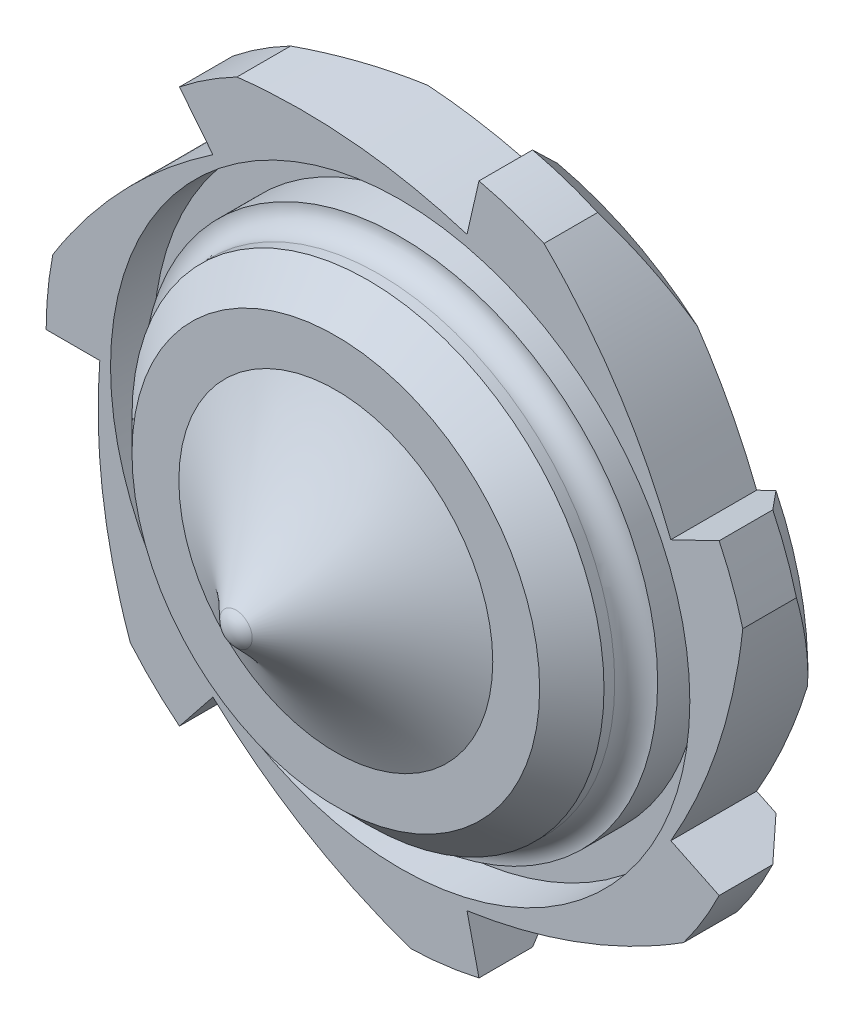
SolidWorks part; units mm, degrees
ref_plane "Plan de face" through (0, 0, 0) normal (0, 0, 1) x (1, 0, 0)
ref_plane "Plan de dessus" through (0, 0, 0) normal (0, 1, 0) x (1, 0, 0)
ref_plane "Plan de droite" through (0, 0, 0) normal (1, 0, 0) x (0, 0, -1)
sketch "Esquisse1" plane through (0, 0, 0) normal (0, 0, 1) x (1, 0, 0)
  line L12 (-10.676, -4.1384) -> (-14.5689, -5.436)
  line L13 (-12.2065, 9.6335) -> (-8.8974, 7.2068)
  line L16 (14.5689, 5.436) -> (10.676, 4.1384)
  line L17 (8.8974, -7.2068) -> (12.2065, -9.6335)
  circle A4 centre (0, 0) radius 33
  arc A9 (-8.8974, 7.2068) -> (-10.676, -4.1384) centre (0, 0) ccw
  arc A10 (-12.2065, 9.6335) -> (-14.5689, -5.436) centre (0, 0) ccw
  arc A13 (8.8974, -7.2068) -> (10.676, 4.1384) centre (0, 0) ccw
  arc A14 (12.2065, -9.6335) -> (14.5689, 5.436) centre (0, 0) ccw
extrude "Boss.-Extru.1" add sketch "Esquisse1" along normal blind 3
sketch "Esquisse2" plane through (0, 0, 3) normal (0, 0, 1) x (1, 0, 0)
  line L1 (-12.1022, -9.7642) -> (-8.8194, -7.3021)
  line L9 (-12.2065, 9.6335) -> (-8.8974, 7.2068)
  line L10 (12.1022, 9.7642) -> (8.8194, 7.3021)
  line L11 (12.2065, -9.6335) -> (8.8974, -7.2068)
  circle A1 centre (0, 0) radius 33
  circle A2 centre (0, 0) radius 33
  arc A10 (-8.8974, 7.2068) -> (-8.8194, -7.3021) centre (0, 0) ccw
  arc A11 (-12.2065, 9.6335) -> (-12.1022, -9.7642) centre (0, 0) ccw
  arc A13 (8.8974, -7.2068) -> (8.8194, 7.3021) centre (0, 0) ccw
  arc A16 (12.2065, -9.6335) -> (12.1022, 9.7642) centre (0, 0) ccw
  point P18 (0, 0)
  dimension "D1" = 0
extrude "Boss.-Extru.2" add sketch "Esquisse2" along normal blind 5
fillet "Congé1" radius 2 2 edges at (-12.6224, -4.7872, 3) (12.6224, 4.7872, 3)
sketch "Esquisse3" plane through (0, 0, 8) normal (0, 0, 1) x (1, 0, 0)
  circle A0 centre (0, 0) radius 22
extrude "Boss.-Extru.3" add sketch "Esquisse3" along normal blind 6
sketch "Esquisse4" plane through (0, 0, 0) normal (0, 1, 0) x (1, 0, 0)
  line L0 (0, -14) -> (0, -23.9364)
  line L1 (-22, -14) -> (22, -14) construction
  line L2 (-14.6319, -14) -> (0, -14)
  arc A0 (-14.6319, -14) -> (-1.5136, -23.3085) centre (-35.2976, -57.0217) cw
  arc A1 (-1.5136, -23.3085) -> (0, -23.9364) centre (0, -21.7981) ccw
revolve "Révolution3" add sketch "Esquisse4" angle 360 about L0
chamfer "Chanfrein1" distance 3 angle 45 1 edges at (33, 0, 0)
fillet "Congé2" radius 2 1 edges at (22, 0, 8)
chamfer "Chanfrein2" distance 3 angle 45 1 edges at (22, 0, 14)
sketch "Esquisse5" plane through (0, 0, 8) normal (0, 0, 1) x (1, 0, 0)
  circle A0 centre (0, 0) radius 24
extrude "Enlèv. de mat.-Extru.-Mince1" cut sketch "Esquisse5" against normal blind 4 thin thin type one direction wall 3
sketch "Esquisse6" plane through (0, 0, 0) normal (0, 0, -1) x (-1, 0, 0)
  line L0 (17.4577, -21.8913) -> (21.7447, -27.267)
  line L1 (28, 0) -> (34.8758, 0)
  line L2 (34.8758, 0) -> (33.6233, -13.0543)
  line L3 (33.6233, -13.0543) -> (23.8928, -24.6154)
  line L4 (21.7447, -27.267) -> (10.7575, -34.427)
  line L5 (10.7575, -34.427) -> (-4.3481, -34.0276)
  line L6 (-6.2306, -27.298) -> (-7.7606, -34.0014)
  line L7 (-7.7606, -34.0014) -> (-20.2089, -29.8755)
  line L8 (-20.2089, -29.8755) -> (-29.3148, -17.8163)
  line L9 (-25.2271, -12.1487) -> (-31.422, -15.132)
  line L10 (-31.422, -15.132) -> (-35.9576, -2.8271)
  line L11 (-35.9576, -2.8271) -> (-32.2069, 11.811)
  line L12 (-25.2271, 12.1487) -> (-31.422, 15.132)
  line L13 (-31.422, 15.132) -> (-24.6295, 26.3502)
  line L14 (-24.6295, 26.3502) -> (-10.8465, 32.5444)
  line L15 (-6.2306, 27.298) -> (-7.7606, 34.0014)
  line L16 (-7.7606, 34.0014) -> (5.2451, 35.6852)
  line L17 (5.2451, 35.6852) -> (18.6816, 28.7712)
  line L18 (17.4577, 21.8913) -> (21.7447, 27.267)
  line L19 (21.7447, 27.267) -> (31.1701, 18.1485)
  line L20 (31.1701, 18.1485) -> (34.142, 3.3327)
  spline S0 degree 2 poles (28, 0) (28.9677, -12.6765) (23.8928, -24.6154) knots 0 0 0 1 1 1
  spline S1 degree 2 poles (17.4577, -21.8913) (8.1501, -30.5515) (-4.3481, -34.0276) knots 0 0 0 1 1 1
  spline S2 degree 2 poles (-6.2306, -27.298) (-18.8046, -25.4206) (-29.3148, -17.8163) knots 0 0 0 1 1 1
  spline S3 degree 2 poles (-25.2271, -12.1487) (-31.5991, -1.1474) (-32.2069, 11.811) knots 0 0 0 1 1 1
  spline S4 degree 2 poles (-25.2271, 12.1487) (-20.5988, 23.9898) (-10.8465, 32.5444) knots 0 0 0 1 1 1
  spline S5 degree 2 poles (-6.2306, 27.298) (5.9128, 31.0622) (18.6816, 28.7712) knots 0 0 0 1 1 1
  spline S6 degree 2 poles (17.4577, 21.8913) (27.972, 14.7442) (34.142, 3.3327) knots 0 0 0 1 1 1
  point P39 (0, 0)
  dimension "D1" = 7
extrude "Enlèv. mat.-Extru.1" cut sketch "Esquisse6" against normal through all both and the other way through all
sketch "Esquisse7" plane through (0, 0, 0) normal (0, 0, -1) x (-1, 0, 0)
  circle A0 centre (0, 0) radius 6.1239
  circle A1 centre (0, 0) radius 21.9305
extrude "Enlèv. de mat.-Extru.-Mince2" cut sketch "Esquisse7" against normal blind 2 thin thin type one direction wall 2
chamfer "Chanfrein3" distance 2 angle 45 1 edges at (-6.1239, 0, 0)
chamfer "Chanfrein4" distance 2 angle 70 1 edges at (-21.9305, 0, 0) first distance on face at (-21.9305, 0, 2)
chamfer "Chanfrein5" distance 4 angle 60 1 edges at (10.552, -8.4201, 0) first distance on face at (16.4356, 0, 0)
chamfer "Chanfrein6" distance 4 angle 60 1 edges at (-10.552, 8.4201, 0) first distance on face at (16.4356, 0, 0)
